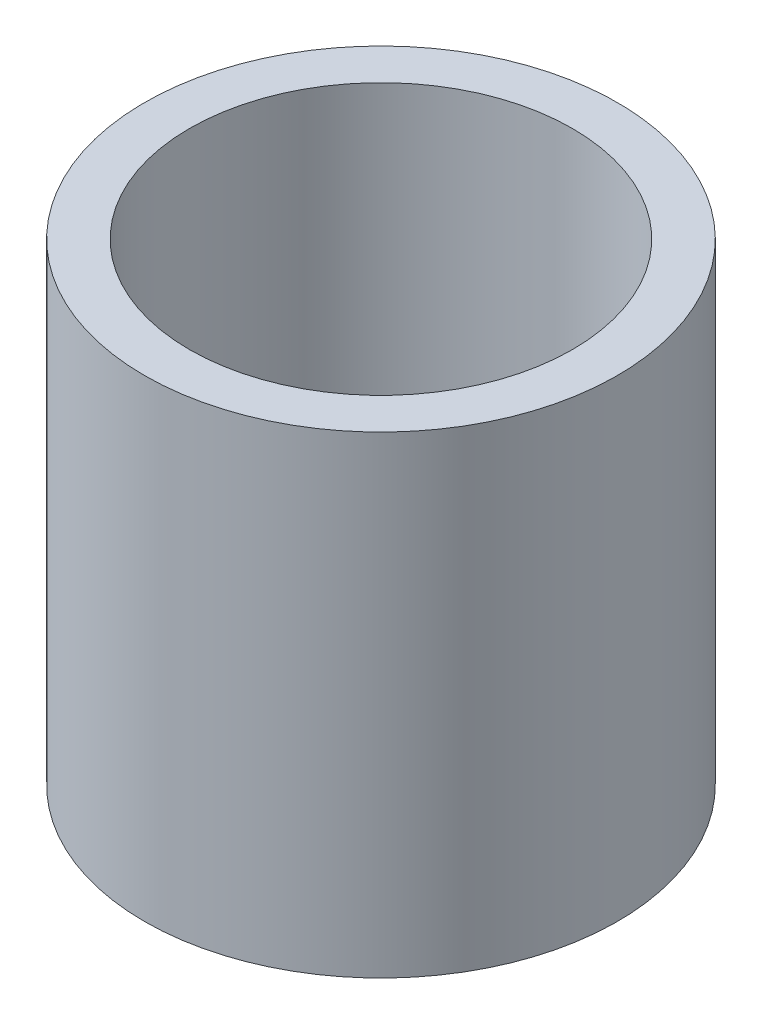
SolidWorks part; units mm, degrees
ref_plane "Front Plane" through (0, 0, 0) normal (0, 0, 1) x (1, 0, 0)
ref_plane "Top Plane" through (0, 0, 0) normal (0, 1, 0) x (1, 0, 0)
ref_plane "Right Plane" through (0, 0, 0) normal (1, 0, 0) x (0, 0, -1)
sketch "Sketch2" plane through (0, 0, 0) normal (0, 0, 1) x (1, 0, 0)
  line L0 (41.148, 0) -> (41.148, -101.6)
  line L1 (41.148, -101.6) -> (50.8, -101.6)
  line L2 (50.8, -101.6) -> (50.8, 0)
  line L3 (50.8, 0) -> (41.148, 0)
  dimension "D1" = 101.6
  dimension "D2" = 9.652
  dimension "D3" = 50.8
ref_axis "Axis1" through (0, 2.54, 0) along (0, -1, 0)
revolve "Revolve1" add sketch "Sketch2" angle 360 about axis through (0, 2.54, 0) along (0, -1, 0)
equation "\"Height\"=4"
equation "\"Radius\"=0.38"
equation "\"D1@Sketch2\"=\"Height\""
equation "\"D2@Sketch2\"=\"Radius\""
